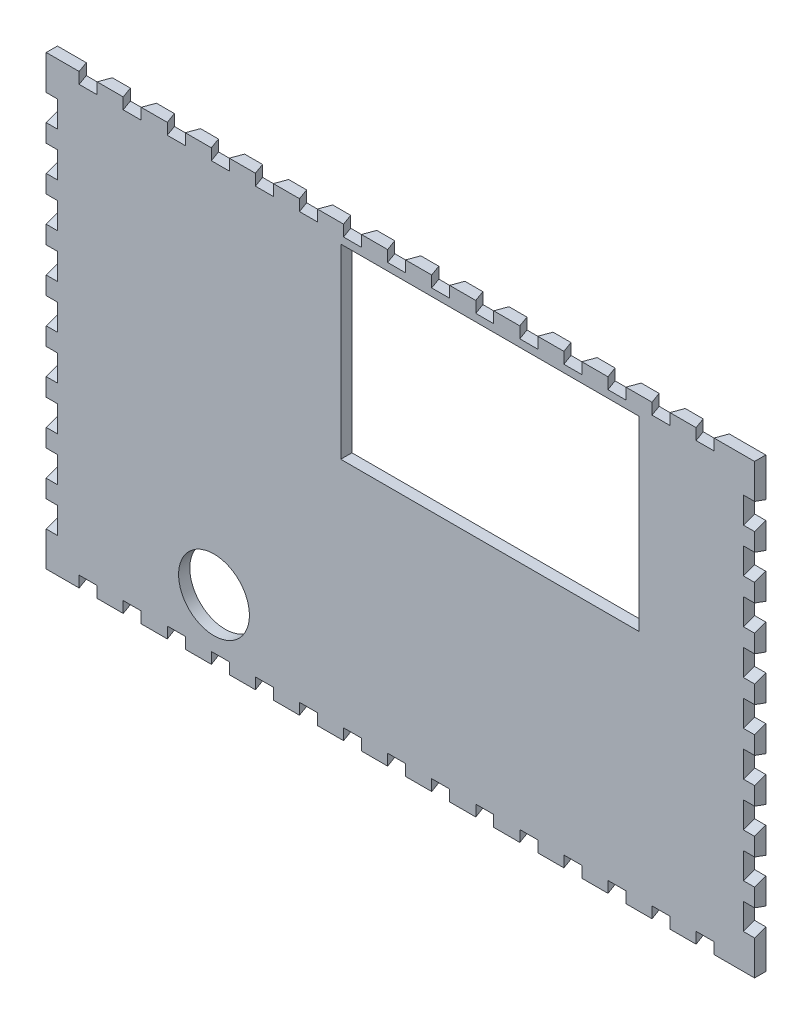
SolidWorks part; units mm, degrees
ref_plane "Front Plane" through (0, 0, 0) normal (0, 0, 1) x (1, 0, 0)
ref_plane "Top Plane" through (0, 0, 0) normal (0, 1, 0) x (1, 0, 0)
ref_plane "Right Plane" through (0, 0, 0) normal (1, 0, 0) x (0, 0, -1)
sketch "Sketch1" plane through (0, 0, 0) normal (0, 0, 1) x (1, 0, 0)
  line L1 (10, 0) -> (190, 0)
  line L56 (190, 120) -> (9.8625, 120)
  line L166 (0, 120) -> (9.8625, 120)
  line L173 (190, 120) -> (190, 0)
  line L174 (0, 120) -> (0, 0)
  line L175 (190, 60) -> (0, 60) construction
  line L176 (0, 0) -> (10, 0)
  line L178 (79, 65) -> (159, 65)
  line L179 (79, 65) -> (79, 115)
  line L180 (79, 115) -> (159, 115)
  line L181 (159, 65) -> (159, 115)
  circle A0 centre (45, 16.5) radius 9.5
  point P13 (0, 0)
  point P14 (0, 0)
  point P15 (44.6727, 32.1352)
  point P16 (0, 0)
  point P18 (0, 21.7095)
  dimension "D3" = 120
  dimension "D4" = 190
  dimension "D5" = 31
  dimension "D6" = 5
  dimension "D7" = 19
  dimension "D1" = 80
  dimension "D2" = 50
  dimension "D8" = 16.5
  dimension "D9" = 45
extrude "Boss-Extrude1" add sketch "Sketch1" along normal blind 3
sketch "Sketch3" plane through (0, 120, 0) normal (0, 1, 0) x (1, 0, 0)
  line L0 (190, 0) -> (0, 0) construction
  line L1 (179.1281, -3) -> (180.22, 0)
  line L2 (173.22, 0) -> (174.3119, -3)
  line L3 (179.1281, -3) -> (174.3119, -3)
  line L4 (180.22, 0) -> (173.22, 0)
  line L5 (167.3081, -3) -> (168.4, 0)
  line L6 (168.4, 0) -> (161.4, 0)
  line L7 (161.4, 0) -> (162.4919, -3)
  line L8 (167.3081, -3) -> (162.4919, -3)
  line L9 (155.4881, -3) -> (156.58, 0)
  line L10 (156.58, 0) -> (149.58, 0)
  line L11 (149.58, 0) -> (150.6719, -3)
  line L12 (155.4881, -3) -> (150.6719, -3)
  line L13 (143.6681, -3) -> (144.76, 0)
  line L14 (144.76, 0) -> (137.76, 0)
  line L15 (137.76, 0) -> (138.8519, -3)
  line L16 (143.6681, -3) -> (138.8519, -3)
  line L17 (131.8481, -3) -> (132.94, 0)
  line L18 (132.94, 0) -> (125.94, 0)
  line L19 (125.94, 0) -> (127.0319, -3)
  line L20 (131.8481, -3) -> (127.0319, -3)
  line L21 (120.0281, -3) -> (121.12, 0)
  line L22 (121.12, 0) -> (114.12, 0)
  line L23 (114.12, 0) -> (115.2119, -3)
  line L24 (120.0281, -3) -> (115.2119, -3)
  line L25 (108.2081, -3) -> (109.3, 0)
  line L26 (109.3, 0) -> (102.3, 0)
  line L27 (102.3, 0) -> (103.3919, -3)
  line L28 (108.2081, -3) -> (103.3919, -3)
  line L29 (96.3881, -3) -> (97.48, 0)
  line L30 (97.48, 0) -> (90.48, 0)
  line L31 (90.48, 0) -> (91.5719, -3)
  line L32 (96.3881, -3) -> (91.5719, -3)
  line L33 (84.5681, -3) -> (85.66, 0)
  line L34 (85.66, 0) -> (78.66, 0)
  line L35 (78.66, 0) -> (79.7519, -3)
  line L36 (84.5681, -3) -> (79.7519, -3)
  line L37 (72.7481, -3) -> (73.84, 0)
  line L38 (73.84, 0) -> (66.84, 0)
  line L39 (66.84, 0) -> (67.9319, -3)
  line L40 (72.7481, -3) -> (67.9319, -3)
  line L41 (60.9281, -3) -> (62.02, 0)
  line L42 (62.02, 0) -> (55.02, 0)
  line L43 (55.02, 0) -> (56.1119, -3)
  line L44 (60.9281, -3) -> (56.1119, -3)
  line L45 (49.1081, -3) -> (50.2, 0)
  line L46 (50.2, 0) -> (43.2, 0)
  line L47 (43.2, 0) -> (44.2919, -3)
  line L48 (49.1081, -3) -> (44.2919, -3)
  line L49 (37.2881, -3) -> (38.38, 0)
  line L50 (38.38, 0) -> (31.38, 0)
  line L51 (31.38, 0) -> (32.4719, -3)
  line L52 (37.2881, -3) -> (32.4719, -3)
  line L53 (25.4681, -3) -> (26.56, 0)
  line L54 (26.56, 0) -> (19.56, 0)
  line L55 (19.56, 0) -> (20.6519, -3)
  line L56 (25.4681, -3) -> (20.6519, -3)
  line L57 (13.6481, -3) -> (14.74, 0)
  line L58 (14.74, 0) -> (7.74, 0)
  line L59 (7.74, 0) -> (8.8319, -3)
  line L60 (13.6481, -3) -> (8.8319, -3)
  line L61 (190, -3) -> (190, 0) construction
  line L63 (190, -3) -> (0, -3) construction
  dimension "D1" = 15
  dimension "D2" = 9.78
  dimension "D3" = 3
  dimension "D4" = 7
  dimension "D5" = 4.8162
  dimension "D6" = 70
  dimension "D7" = 70
extrude "Cut-Extrude1" cut sketch "Sketch3" against normal blind 3
extrude "Cut-Extrude3" cut sketch "Sketch3<2>" against normal blind 187 from offset 117 offset against normal yes
sketch "Sketch3<2>" plane through (0, 120, 0) normal (0, 1, 0) x (1, 0, 0) same geometry as "Sketch3"
sketch "Sketch6" plane through (0, 0, 0) normal (-1, 0, 0) x (0, 0, 1)
  line L0 (0, 104.7919) -> (3, 103.7)
  line L1 (3, 110.7) -> (0, 109.6081)
  line L2 (0, 104.7919) -> (0, 109.6081)
  line L3 (3, 103.7) -> (3, 110.7)
  line L5 (0, 120) -> (0, 0) construction
  line L6 (0, 92.9919) -> (3, 91.9)
  line L7 (3, 91.9) -> (3, 98.9)
  line L8 (3, 98.9) -> (0, 97.8081)
  line L9 (0, 92.9919) -> (0, 97.8081)
  line L10 (0, 81.1919) -> (3, 80.1)
  line L11 (3, 80.1) -> (3, 87.1)
  line L12 (3, 87.1) -> (0, 86.0081)
  line L13 (0, 81.1919) -> (0, 86.0081)
  line L14 (0, 69.3919) -> (3, 68.3)
  line L15 (3, 68.3) -> (3, 75.3)
  line L16 (3, 75.3) -> (0, 74.2081)
  line L17 (0, 69.3919) -> (0, 74.2081)
  line L18 (0, 57.5919) -> (3, 56.5)
  line L19 (3, 56.5) -> (3, 63.5)
  line L20 (3, 63.5) -> (0, 62.4081)
  line L21 (0, 57.5919) -> (0, 62.4081)
  line L22 (0, 45.7919) -> (3, 44.7)
  line L23 (3, 44.7) -> (3, 51.7)
  line L24 (3, 51.7) -> (0, 50.6081)
  line L25 (0, 45.7919) -> (0, 50.6081)
  line L26 (0, 33.9919) -> (3, 32.9)
  line L27 (3, 32.9) -> (3, 39.9)
  line L28 (3, 39.9) -> (0, 38.8081)
  line L29 (0, 33.9919) -> (0, 38.8081)
  line L30 (0, 22.1919) -> (3, 21.1)
  line L31 (3, 21.1) -> (3, 28.1)
  line L32 (3, 28.1) -> (0, 27.0081)
  line L33 (0, 22.1919) -> (0, 27.0081)
  line L34 (0, 10.3919) -> (3, 9.3)
  line L35 (3, 9.3) -> (3, 16.3)
  line L36 (3, 16.3) -> (0, 15.2081)
  line L37 (0, 10.3919) -> (0, 15.2081)
  line L38 (3, 120) -> (0, 120) construction
  dimension "D2" = 3
  dimension "D3" = 7
  dimension "D4" = 4.8162
  dimension "D5" = 3
  dimension "D6" = 70
  dimension "D7" = 70
  dimension "D8" = 9.3
  dimension "D9" = 9.3
  dimension "D1" = 9
extrude "Cut-Extrude5" cut sketch "Sketch6" against normal blind 3
extrude "Cut-Extrude6" cut sketch "Sketch6<3>" against normal blind 3 from offset 187 offset against normal yes
sketch "Sketch6<3>" plane through (0, 0, 0) normal (-1, 0, 0) x (0, 0, 1) same geometry as "Sketch6"
